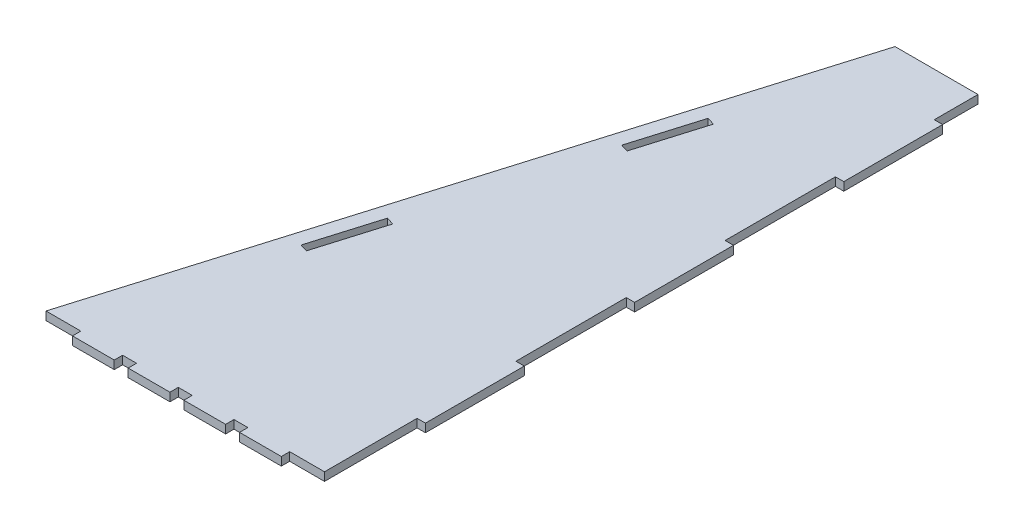
SolidWorks part; units mm, degrees
ref_plane "Front Plane" through (0, 0, 0) normal (0, 0, 1) x (1, 0, 0)
ref_plane "Top Plane" through (0, 0, 0) normal (0, 1, 0) x (1, 0, 0)
ref_plane "Right Plane" through (0, 0, 0) normal (1, 0, 0) x (0, 0, -1)
sketch "Sketch1" plane through (0, 0, 0) normal (0, 1, 0) x (1, 0, 0)
  line L0 (200, 469.3) -> (140.4365, 469.3)
  line L1 (0, 0) -> (200, 0)
  line L4 (200, 0) -> (200, 469.3)
  line L5 (0, 0) -> (200, 469.3) construction
  line L6 (83.195, 278.0149) -> (200, 0) construction
  line L7 (140.4365, 469.3) -> (0, 0)
  point P4 (100.7122, 236.3212)
  dimension "D1" = 469.3
  dimension "D2" = 200
extrude "Boss-Extrude1" add sketch "Sketch1" along normal blind 6
sketch "Sketch2" plane through (200, 0, 0) normal (1, 0, 0) x (0, 0, -1)
  line L0 (0, 6) -> (469.3, 6) construction
  line L1 (437.9, 6) -> (366.9, 6)
  line L2 (437.9, 6) -> (437.9, 0)
  line L3 (437.9, 0) -> (366.9, 0)
  line L4 (366.9, 6) -> (366.9, 0)
  line L5 (437.9, 6) -> (366.9, 0) construction
  line L6 (437.9, 0) -> (366.9, 6) construction
  line L7 (0, 0) -> (469.3, 0) construction
  line L8 (469.3, 6) -> (469.3, 0) construction
  line L9 (287.7, 6) -> (287.7, 0)
  line L10 (287.7, 6) -> (216.7, 6)
  line L11 (216.7, 6) -> (216.7, 0)
  line L12 (287.7, 0) -> (216.7, 0)
  line L13 (137.5, 6) -> (137.5, 0)
  line L14 (137.5, 6) -> (66.5, 6)
  line L15 (66.5, 6) -> (66.5, 0)
  line L16 (137.5, 0) -> (66.5, 0)
  point P4 (402.4, 3)
  dimension "D1" = 71
  dimension "D2" = 31.4
  dimension "D4" = 79.2
  dimension "D3" = 3
extrude "Boss-Extrude2" add sketch "Sketch2" along normal blind 6
sketch "Sketch4" plane through (0, 6, 0) normal (0, 1, 0) x (1, 0, 0)
  line L0 (123.4459, 355.8811) -> (117.8893, 357.5439)
  line L1 (140.4365, 469.3) -> (0, 0) construction
  line L2 (93.6124, 312.8267) -> (103.6124, 309.8343) construction
  line L3 (103.6124, 309.8343) -> (117.8893, 357.5439)
  line L5 (123.4459, 355.8811) -> (109.1689, 308.1715)
  line L6 (109.1689, 308.1715) -> (103.6124, 309.8343)
  line L7 (56.132, 130.9369) -> (50.5755, 132.5997)
  line L8 (70.409, 178.6466) -> (56.132, 130.9369)
  line L9 (70.409, 178.6466) -> (64.8525, 180.3093)
  line L10 (50.5755, 132.5997) -> (64.8525, 180.3093)
  dimension "D2" = 90
  dimension "D3" = 10
  dimension "D4" = 360
  dimension "D5" = 90
  dimension "D6" = 180
  dimension "D7" = 49.8
  dimension "D9" = 5.8
  dimension "D8" = 2
extrude "Cut-Extrude1" cut sketch "Sketch4" against normal blind 6
sketch "Sketch5" plane through (0, 0, 0) normal (0, -1, 0) x (1, 0, 0)
  line L0 (0, 0) -> (200, 0) construction
  line L1 (175, 0) -> (145, 0)
  line L2 (175, 0) -> (175, 6)
  line L3 (175, 6) -> (145, 6)
  line L4 (145, 0) -> (145, 6)
  line L5 (175, 0) -> (145, 6) construction
  line L6 (175, 6) -> (145, 0) construction
  line L7 (200, 0) -> (200, -66.5) construction
  line L8 (135, 0) -> (135, 6)
  line L9 (135, 0) -> (105, 0)
  line L10 (105, 0) -> (105, 6)
  line L11 (135, 6) -> (105, 6)
  line L12 (95, 0) -> (95, 6)
  line L13 (95, 0) -> (65, 0)
  line L14 (65, 0) -> (65, 6)
  line L15 (95, 6) -> (65, 6)
  line L16 (55, 0) -> (55, 6)
  line L17 (55, 0) -> (25, 0)
  line L18 (25, 0) -> (25, 6)
  line L19 (55, 6) -> (25, 6)
  point P4 (160, 3)
  dimension "D1" = 30
  dimension "D2" = 25
  dimension "D4" = 6
  dimension "D3" = 4
extrude "Boss-Extrude3" add sketch "Sketch5" against normal blind 6 separate body
combine bodies "Combine1" operation type add bodies to combine 105 104 106 107 103
sketch "Sketch7" plane through (0, 6, 0) normal (0, 1, 0) x (1, 0, 0)
  line L0 (160, -6) -> (200, -6)
  line L1 (175, -6) -> (145, -6) construction
  dimension "D1" = 40
